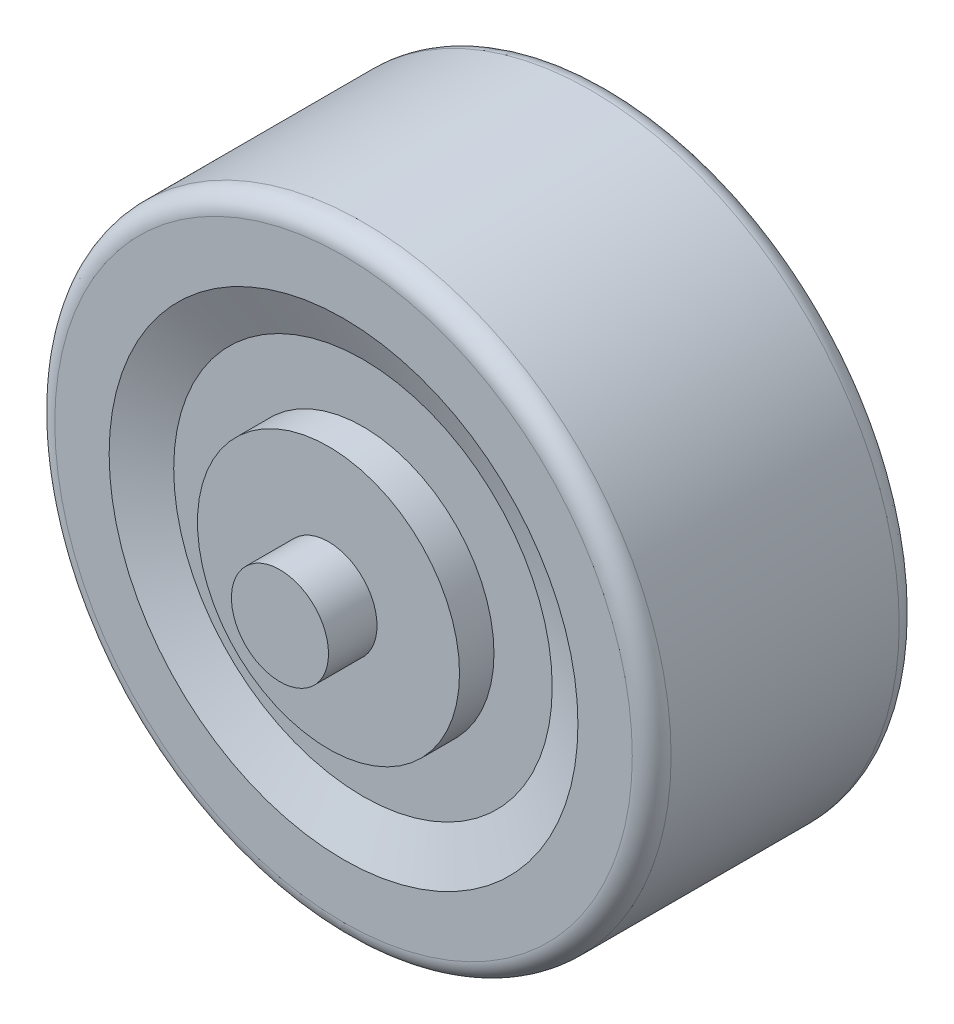
SolidWorks part; units mm, degrees
ref_plane "Front Plane" through (0, 0, 0) normal (0, 0, 1) x (1, 0, 0)
ref_plane "Top Plane" through (0, 0, 0) normal (0, 1, 0) x (1, 0, 0)
ref_plane "Right Plane" through (0, 0, 0) normal (1, 0, 0) x (0, 0, -1)
sketch "Sketch3" plane through (0, 0, 0) normal (0, 1, 0) x (1, 0, 0)
  line L1 (6.75, 7.65) -> (6.75, 5.875)
  line L2 (6.75, 5.875) -> (9.75, 5.875)
  line L3 (9.75, 5.875) -> (12.075, 6.875)
  line L4 (12.075, 6.875) -> (15.875, 6.875)
  line L5 (15.875, 6.875) -> (15.875, 0)
  line L6 (15.875, 0) -> (0, 0)
  line L7 (0, 0) -> (0, 10.15)
  line L8 (0, 0) -> (0, 18.3822) construction
  line L9 (0, 0) -> (21.3923, 0) construction
  line L10 (6.75, 7.65) -> (2.5, 7.65)
  line L11 (2.5, 7.65) -> (2.5, 10.15)
  line L12 (2.5, 10.15) -> (0, 10.15)
  dimension "D1" = 15.875
  dimension "D2" = 10.15
  dimension "D3" = 6.75
  dimension "D4" = 7.65
  dimension "D5" = 6.875
  dimension "D6" = 2.5
  dimension "D7" = 3.8
  dimension "D8" = 1
  dimension "D9" = 3
revolve "Revolve1" add sketch "Sketch3" angle 360 about L8
mirror "Mirror1" about plane through (0, 0, 0) normal (0, 0, 1) of "Revolve1"
fillet "Fillet1" radius 1 2 edges at (15.875, 0, -6.875) (15.875, 0, 6.875)
ref_plane "Plane1" through (-15.875, 0, 0) normal (-1, 0, 0) x (0, 0, 1)
ref_plane "Plane2" through (26.725, 0, 0) normal (-1, 0, 0) x (0, 0, 1)
ref_plane "Plane3" through (0, 0, 0) normal (0, 1, 0) x (1, 0, 0)
ref_plane "Plane4" through (0, 9.7, 0) normal (0, 1, 0) x (1, 0, 0)
ref_axis "Axis1" through (26.725, 9.7, -11.1184) along (0, 0, 1)
ref_axis "Axis2" through (17.4625, 9.7, 0) along (-1, 0, 0)
